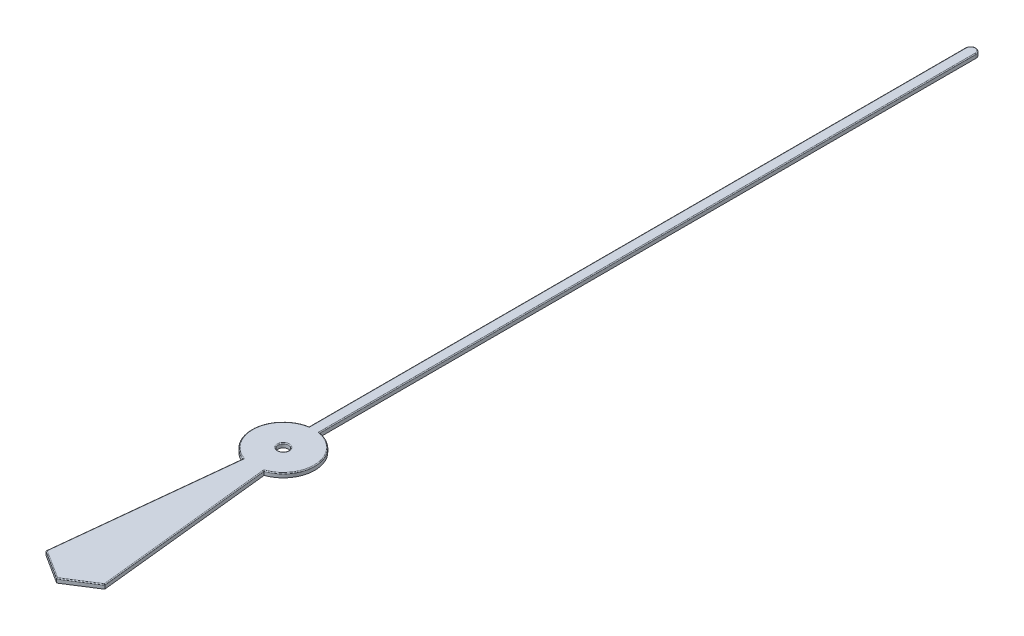
SolidWorks part; units mm, degrees
ref_plane "前视基准面" through (0, 0, 0) normal (0, 0, 1) x (1, 0, 0)
ref_plane "上视基准面" through (0, 0, 0) normal (0, 1, 0) x (1, 0, 0)
ref_plane "右视基准面" through (0, 0, 0) normal (1, 0, 0) x (0, 0, -1)
sketch "草图3" plane through (0, 0, 0) normal (0, 1, 0) x (1, 0, 0)
  line L0 (0, 0) -> (0, 16.5) construction
  line L1 (0, 0) -> (0, -5.4) construction
  line L2 (0.125, 0.7395) -> (0.125, 16.5)
  line L3 (-0.125, 0.7395) -> (-0.125, 16.5)
  line L4 (-0.25, -0.7071) -> (-0.7, -4.9541)
  line L5 (-0.7, -4.9541) -> (0, -5.4)
  line L6 (0.7, -4.9541) -> (0, -5.4)
  line L7 (0.25, -0.7071) -> (0.7, -4.9541)
  line L8 (-0.125, 16.5) -> (0.125, 16.5)
  line L10 (-0.125, 0) -> (-0.125, 16.5) construction
  line L11 (0.125, 0) -> (0.125, 16.5) construction
  arc A0 (0.25, -0.7071) -> (0.125, 0.7395) centre (0, 0) ccw
  arc A1 (-0.125, 0.7395) -> (-0.25, -0.7071) centre (0, 0) ccw
  circle A2 centre (0, 0) radius 0.125
  dimension "D1" = 1.5
  dimension "D9" = 0.25
  dimension "D2" = 16.5
  dimension "D3" = 5.4
  dimension "D6" = 0.5
  dimension "D7" = 1.4
  dimension "D8" = 115
  dimension "D4" = 0.125
  dimension "D5" = 0.125
extrude "凸台-拉伸1" add sketch "草图3" along normal blind 0.1
fillet "圆角1" radius 0.125 2 edges at (-0.125, 0.05, -16.5) (0.125, 0.05, -16.5)
fillet "圆角2" radius 0.02 11 edges at (0, 0.1, 0.125) (0.125, 0.1, -8.5573) (0.7472, 0.1, -0.0646) (0.475, 0.1, 2.8306) (0.35, 0.1, 5.177) (-0.35, 0.1, 5.177) (-0.475, 0.1, 2.8306) (-0.7472, 0.1, -0.0646) (-0.125, 0.1, -8.5573) (-0.0884, 0.1, -16.4634) (0.0884, 0.1, -16.4634)
